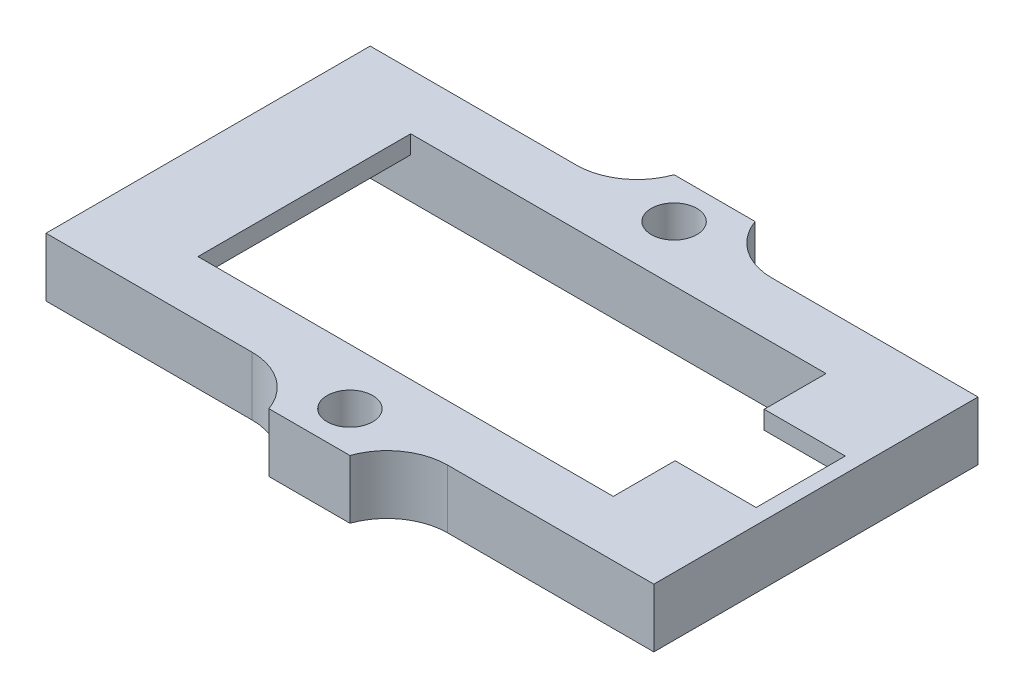
SolidWorks part; units mm, degrees
ref_plane "Plano frontal" through (0, 0, 0) normal (0, 0, 1) x (1, 0, 0)
ref_plane "Plano superior" through (0, 0, 0) normal (0, 1, 0) x (1, 0, 0)
ref_plane "Plano direito" through (0, 0, 0) normal (1, 0, 0) x (0, 0, -1)
sketch "Esboço1" plane through (0, 0, 0) normal (0, 1, 0) x (1, 0, 0)
  line L0 (0, 16) -> (0, -16) construction
  line L1 (-30, -16) -> (30, -16)
  line L2 (-30, -16) -> (-30, 16)
  line L3 (-30, 16) -> (30, 16)
  line L4 (30, -16) -> (30, 16)
  line L5 (-30, -16) -> (30, 16) construction
  line L6 (-30, 16) -> (30, -16) construction
  line L7 (-30, 0) -> (30, 0) construction
  line L8 (-4, 12) -> (4, 12)
  line L9 (-4, 12) -> (-4, 20)
  line L10 (-4, 20) -> (4, 20)
  line L11 (4, 12) -> (4, 20)
  line L12 (-4, 12) -> (4, 20) construction
  line L13 (-4, 20) -> (4, 12) construction
  line L14 (-4, -12) -> (4, -20) construction
  line L15 (-4, -20) -> (4, -12) construction
  line L16 (4, -12) -> (4, -20)
  line L17 (-4, -12) -> (4, -12)
  line L18 (-4, -12) -> (-4, -20)
  line L19 (-4, -20) -> (4, -20)
  circle A0 centre (0, 16) radius 2.25
  circle A1 centre (0, -16) radius 2.25
  point P0 (0, 0)
  dimension "D5" = 4.5
  dimension "D1" = 60
  dimension "D2" = 32
  dimension "D3" = 8
  dimension "D4" = 8
extrude "Ressalto-extrusão1" add sketch "Esboço1" along normal blind 5.8 contours A0 L3 L11 L10 L9 | A0 L3 L9 L8 L11 | L18 L17 L16 L1 L4 L3 L11 L8 L9 L2 | L1 A1 L16 L17 L18 | L1 A1 L18 L19 L16 region at (0, 0, 0) region at (0, 0, 13.6544) region at (0, 0, 18.3456) region at (0, 0, -18.3456) region at (0, 0, -13.6544)
sketch "Esboço2" plane through (0, 5.8, 0) normal (0, 1, 0) x (1, 0, 0)
  line L1 (-20.5, -10.5) -> (20.5, -10.5)
  line L2 (-20.5, -10.5) -> (-20.5, 10.5)
  line L3 (-20.5, 10.5) -> (20.5, 10.5)
  line L4 (20.5, -10.5) -> (20.5, 10.5)
  line L5 (-20.5, -10.5) -> (20.5, 10.5) construction
  line L6 (-20.5, 10.5) -> (20.5, -10.5) construction
  point P0 (0, 0)
  dimension "D1" = 21
  dimension "D2" = 41
extrude "Corte-extrusão1" cut sketch "Esboço2" against normal through all
fillet "Filete1" radius 6 4 edges at (4, 2.9, -16) (-4, 2.9, -16) (-4, 2.9, 16) (4, 2.9, 16)
sketch "Esboço4" plane through (0, 0, 0) normal (0, -1, 0) x (1, 0, 0)
  line L0 (-30, 0) -> (30, 0) construction
  line L1 (-30, 16) -> (-30, -16) construction
  line L2 (30, 16) -> (30, -16) construction
  line L3 (-20.5, 10.5) -> (20.5, 10.5) construction
  line L4 (-28.5, -10.5) -> (28.5, -10.5)
  line L5 (-28.5, -10.5) -> (-28.5, 10.5)
  line L6 (-28.5, 10.5) -> (28.5, 10.5)
  line L7 (28.5, -10.5) -> (28.5, 10.5)
  line L8 (-28.5, -10.5) -> (28.5, 10.5) construction
  line L9 (-28.5, 10.5) -> (28.5, -10.5) construction
  line L10 (-20.5, -10.5) -> (-20.5, 10.5) construction
  point P6 (0, 0)
  dimension "D1" = 8
extrude "Corte-extrusão2" cut sketch "Esboço4" against normal blind 4
sketch "Esboço5" plane through (0, 4, 0) normal (0, -1, 0) x (1, 0, 0)
  line L0 (20.5, -10.5) -> (20.5, 10.5) construction
  line L1 (12.5, 4.4) -> (28.5, 4.4)
  line L2 (12.5, 4.4) -> (12.5, -4.4)
  line L3 (12.5, -4.4) -> (28.5, -4.4)
  line L4 (28.5, 4.4) -> (28.5, -4.4)
  line L5 (12.5, 4.4) -> (28.5, -4.4) construction
  line L6 (12.5, -4.4) -> (28.5, 4.4) construction
  line L7 (28.5, -10.5) -> (28.5, 10.5) construction
  point P0 (20.5, 0)
  dimension "D1" = 8.8
extrude "Corte-extrusão3" cut sketch "Esboço5" against normal blind 10
